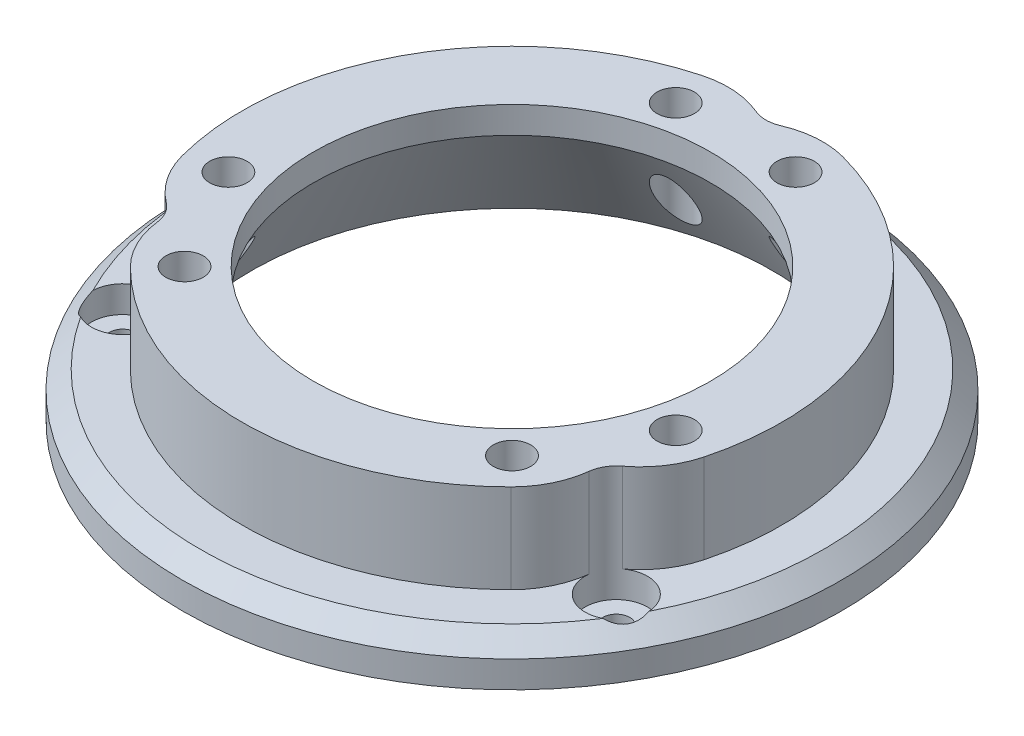
SolidWorks part; units mm, degrees
ref_plane "Front Plane" through (0, 0, 0) normal (0, 0, 1) x (1, 0, 0)
ref_plane "Top Plane" through (0, 0, 0) normal (0, 1, 0) x (1, 0, 0)
ref_plane "Right Plane" through (0, 0, 0) normal (1, 0, 0) x (0, 0, -1)
sketch "Sketch1" plane through (0, 0, 0) normal (0, 1, 0) x (1, 0, 0)
  circle A0 centre (0, 0) radius 30.3
  circle A1 centre (0, 0) radius 22.3
  dimension "D1" = 60.6
  dimension "D2" = 8
extrude "Boss-Extrude1" add sketch "Sketch1" along normal blind 10
sketch "Sketch2" plane through (0, 0, 0) normal (0, 1, 0) x (1, 0, 0)
  circle A0 centre (0, 0) radius 37
  circle A1 centre (0, 0) radius 22.3
  circle A2 centre (0, 0) radius 22.3 construction
  dimension "D1" = 74
extrude "Boss-Extrude2" add sketch "Sketch2" against normal blind 5
sketch "Sketch3" plane through (0, 0, 0) normal (0, 1, 0) x (1, 0, 0)
  circle A0 centre (0, 32) radius 1.5
  dimension "D2" = 3
  dimension "D1" = 32
extrude "Cut-Extrude1" cut sketch "Sketch3" against normal through all
sketch "Sketch4" plane through (0, 0, 0) normal (0, 1, 0) x (1, 0, 0)
  circle A0 centre (0, 32) radius 3.5
  dimension "D1" = 7
extrude "Cut-Extrude2" cut sketch "Sketch4" against normal blind 3 and the other way through all
pattern_circular "CirPattern1" count 3 over 360 about axis through (0, -5, 0) along (0, 1, 0) of "Cut-Extrude1", "Cut-Extrude2"
chamfer "Chamfer1" distance 12 angle 30 1 edges at (0, -5, 22.3) first distance on face at (0, 10, 22.3)
chamfer "Chamfer2" distance 2 angle 45 1 edges at (0, 0, 37)
sketch "Sketch5" plane through (0, 10, 0) normal (0, 1, 0) x (1, 0, 0)
  line L0 (6.7293, 25.1141) -> (0, 0) construction
  line L1 (0, 0) -> (0, 32) construction
  circle A0 centre (6.7293, 25.1141) radius 2.1
  circle A1 centre (-6.7293, 25.1141) radius 2.1
  point P8 (0, 0)
  dimension "D2" = 4.2
  dimension "D1" = 15
  dimension "D3" = 26
extrude "Cut-Extrude3" cut sketch "Sketch5" against normal through all
pattern_circular "CirPattern2" count 3 over 360 about axis through (0, 10, 0) along (0, -1, 0) of "Cut-Extrude3" reverse direction yes
fillet "Fillet1" radius 10 6 edges at (27.6006, 5, 12.5018) (24.6272, 5, 17.652) (-24.6272, 5, 17.652) (-27.6006, 5, 12.5018) (-2.9734, 5, -30.1537) (2.9734, 5, -30.1537)
